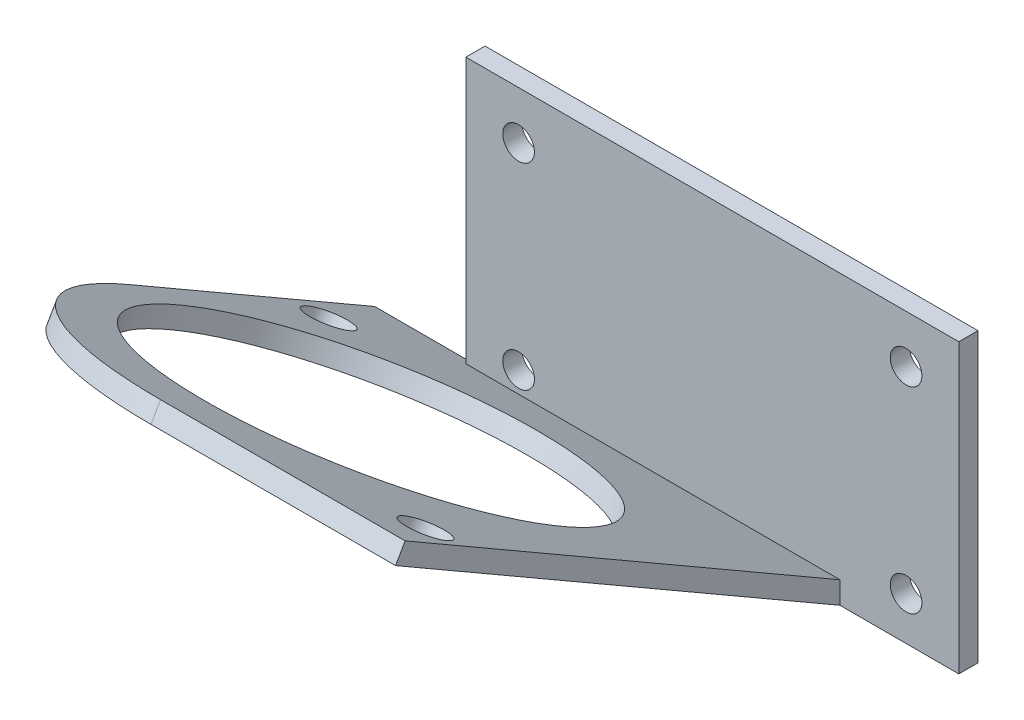
SolidWorks part; units mm, degrees
material "PTFE (general)"
ref_plane "Front Plane" through (0, 0, 0) normal (0, 0, 1) x (1, 0, 0)
ref_plane "Top Plane" through (0, 0, 0) normal (0, 1, 0) x (1, 0, 0)
ref_plane "Right Plane" through (0, 0, 0) normal (1, 0, 0) x (0, 0, -1)
sketch "Sketch1" plane through (0, 0, 0) normal (0, 0, 1) x (1, 0, 0)
  line L1 (0, 0) -> (51.4, 0)
  line L2 (0, 0) -> (0, 30)
  line L3 (0, 30) -> (51.4, 30)
  line L4 (51.4, 0) -> (51.4, 30)
  line L5 (0, 0) -> (51.4, 30) construction
  line L6 (0, 30) -> (51.4, 0) construction
  point P4 (25.7, 15)
  dimension "D1" = 51.4
  dimension "D2" = 30
extrude "Boss-Extrude1" add sketch "Sketch1" along normal blind 2
sketch "Sketch2" plane through (0, 0, 0) normal (0, 0, -1) x (-1, 0, 0)
  circle A0 centre (-45.9, 25) radius 1.65
  circle A1 centre (-5.5, 25) radius 1.65
  circle A2 centre (-5.5, 4.5) radius 1.65
  circle A3 centre (-45.9, 4.5) radius 1.65
  dimension "D1" = 3.3
extrude "Cut-Extrude1" cut sketch "Sketch2" against normal blind 10
ref_plane "Plane1" through (0, -0.866, 0.5) normal (0, -0.866, 0.5) x (1, 0, 0)
sketch "Sketch3" plane through (0, -0.866, 0.5) normal (0, -0.866, 0.5) x (1, 0, 0)
  line L0 (0, 16.7321) -> (0, 1.7321) construction
  line L1 (39, 1.7321) -> (-10.5, 1.7321)
  line L2 (39, 1.7321) -> (39, 55.2321)
  line L3 (39, 55.2321) -> (-10.5, 55.2321)
  line L4 (-10.5, 1.7321) -> (-10.5, 55.2321)
  line L5 (39, 1.7321) -> (-10.5, 55.2321) construction
  line L6 (39, 55.2321) -> (-10.5, 1.7321) construction
  line L9 (0, 1.7321) -> (51.4, 1.7321) construction
  point P4 (14.25, 28.4821)
  dimension "D1" = 49.5
  dimension "D2" = 53.5
  dimension "D3" = 10.5
extrude "Boss-Extrude2" add sketch "Sketch3" against normal blind 2
fillet "Fillet1" radius 24 1 edges at (-10.5, 27.616, 47.8324)
sketch "Sketch5" plane through (0, -0.866, 0.5) normal (0, -0.866, 0.5) x (1, 0, 0)
  circle A0 centre (35.9, 49.2108) radius 2.25
  circle A1 centre (-7.1, 11.2108) radius 2.25
  point P4 (-7.1, 11.2108)
  point P5 (35.9, 49.2108)
extrude "Cut-Extrude2" cut sketch "Sketch5" against normal blind 2
sketch "Sketch6" plane through (0, -0.866, 0.5) normal (0, -0.866, 0.5) x (1, 0, 0)
  circle A0 centre (12.9, 29.2108) radius 20
  point P2 (12.9, 29.2108)
  dimension "D1" = 40
extrude "Cut-Extrude3" cut sketch "Sketch6" against normal blind 2
